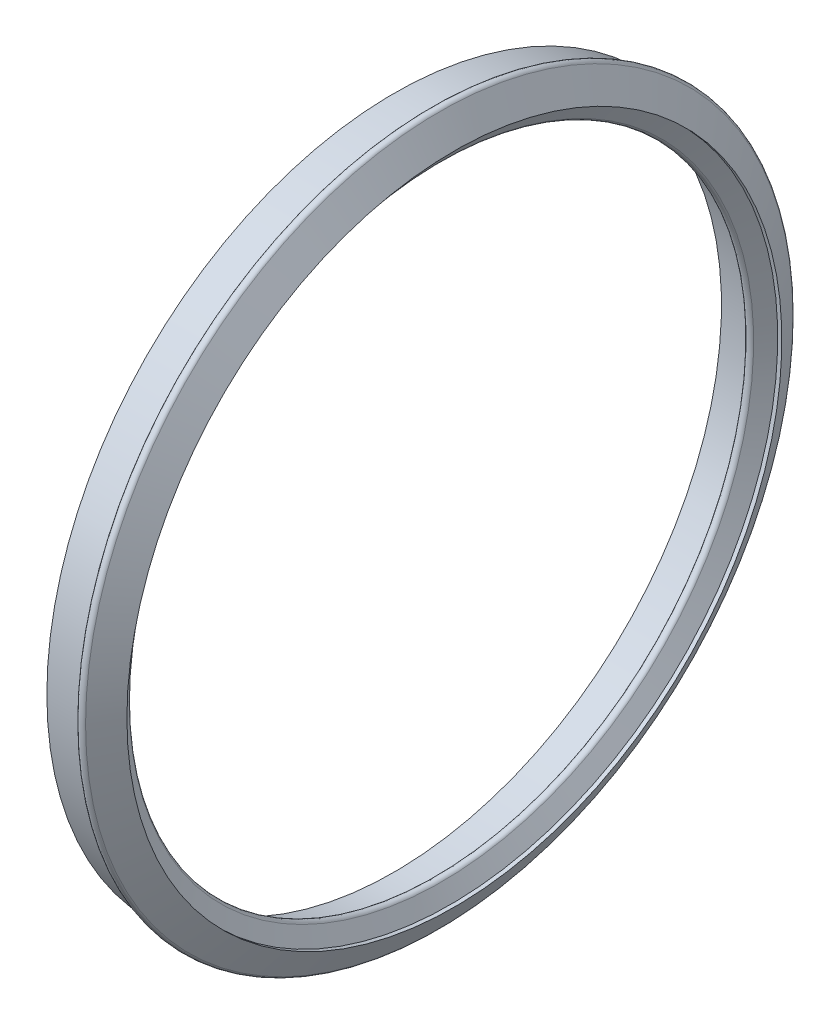
SolidWorks part; units mm, degrees
ref_plane "Спереди" through (0, 0, 0) normal (0, 0, 1) x (1, 0, 0)
ref_plane "Сверху" through (0, 0, 0) normal (0, 1, 0) x (1, 0, 0)
ref_plane "Справа" through (0, 0, 0) normal (1, 0, 0) x (0, 0, -1)
sketch "Эскиз1" plane through (0, 0, 0) normal (0, 0, 1) x (1, 0, 0)
  line L0 (0, 20) -> (1.5536, 20)
  line L1 (1.5536, 20) -> (1.7268, 20.3)
  line L2 (0, 19.1) -> (1.4226, 19.1)
  line L3 (1.4226, 19.1) -> (1.8268, 18.4)
  line L4 (2.1732, 18.4) -> (2.5774, 19.1)
  line L5 (2.0732, 20.3) -> (2.766, 19.1)
  line L6 (2.5774, 19.1) -> (2.766, 19.1)
  line L7 (0, 20) -> (0, 19.1)
  line L8 (0, 4.1) -> (22.375, 4.1) construction
  line L10 (7.9301, 24.1) -> (-9.4603, 24.1) construction
  line L11 (0, 15.9) -> (0, 24.1) construction
  arc A0 (1.8268, 18.4) -> (2.1732, 18.4) centre (2, 18.5) ccw
  arc A1 (2.0732, 20.3) -> (1.7268, 20.3) centre (1.9, 20.2) ccw
  point P12 (2, 18.1)
  point P17 (1.9, 20.6)
  dimension "D10" = 0.2
  dimension "D1" = 1
  dimension "D2" = 60
  dimension "D3" = 60
  dimension "D4" = 2
  dimension "D5" = 1.9
  dimension "D6" = 30
  dimension "D7" = 30
  dimension "D8" = 15
  dimension "D9" = 0.9
  dimension "D11" = 20
revolve "Повернуть1" add sketch "Эскиз1" angle 360 about L8
sketch "Эскиз2" plane through (0, 0, 0) normal (0, 0, 1) x (1, 0, 0)
  line L4 (0, 0) -> (4.5339, 0) construction
revolve "Повернуть2" add sketch "Эскиз2" angle 360 about L4 rebuild error yes
